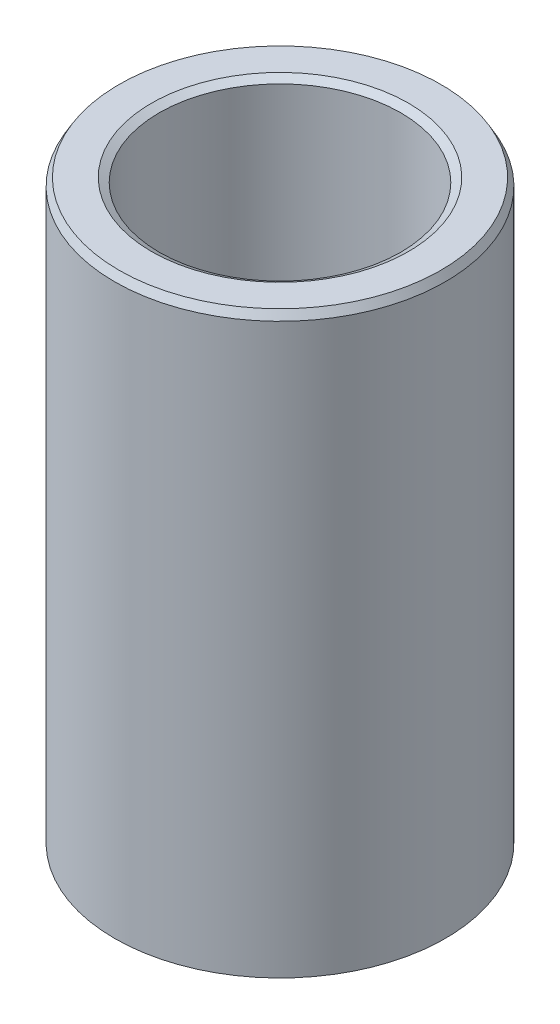
SolidWorks part; units mm, degrees
ref_plane "Front Plane" through (0, 0, 0) normal (0, 0, 1) x (1, 0, 0)
ref_plane "Top Plane" through (0, 0, 0) normal (0, 1, 0) x (1, 0, 0)
ref_plane "Right Plane" through (0, 0, 0) normal (1, 0, 0) x (0, 0, -1)
sketch "Sketch1" plane through (0, 0, 0) normal (0, 1, 0) x (1, 0, 0)
  circle A0 centre (0, 0) radius 20
  dimension "SLEEVE_OD" = 40
extrude "Boss-Extrude1" add sketch "Sketch1" along normal blind 70.2381
sketch "Sketch2" plane through (0, 0, 0) normal (0, 1, 0) x (1, 0, 0)
  circle A0 centre (0, 0) radius 14.6052
  dimension "BORE_D" = 29.2103
extrude "Cut-Extrude1" cut sketch "Sketch2" along normal through all
chamfer "Chamfer1" distance 0.9349 angle 30 4 edges at (0, 70.2381, 14.6052) (0, 0, 14.6052) (0, 0, 20) (0, 70.2381, 20) first distance on face at (0, 70.2381, 14.6052) first distance on face at (0, 0, 14.6052) first distance on face at (0, 70.2381, 20)
